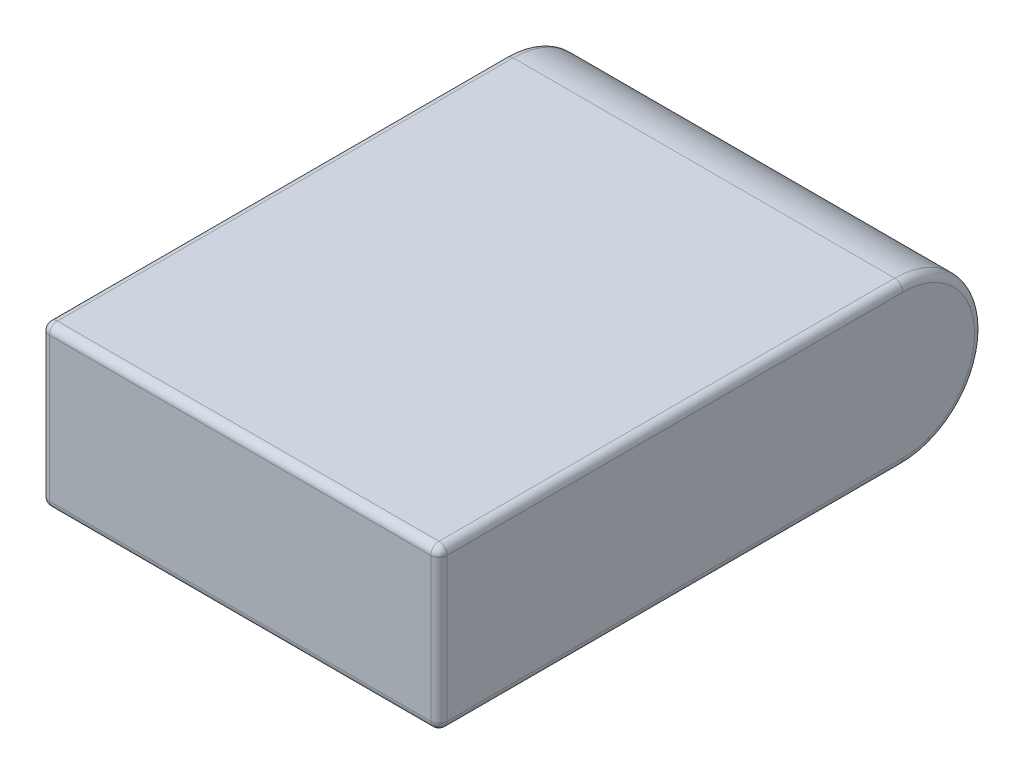
SolidWorks part; units mm, degrees
ref_plane "Front Plane" through (0, 0, 0) normal (0, 0, 1) x (1, 0, 0)
ref_plane "Top Plane" through (0, 0, 0) normal (0, 1, 0) x (1, 0, 0)
ref_plane "Right Plane" through (0, 0, 0) normal (1, 0, 0) x (0, 0, -1)
sketch "Sketch1" plane through (0, 0, 0) normal (0, 1, 0) x (1, 0, 0)
  line L1 (-24.5, 33.5) -> (24.5, 33.5)
  line L2 (-24.5, 33.5) -> (-24.5, -33.5)
  line L3 (-24.5, -33.5) -> (24.5, -33.5)
  line L4 (24.5, 33.5) -> (24.5, -33.5)
  line L5 (-24.5, 33.5) -> (24.5, -33.5) construction
  line L6 (-24.5, -33.5) -> (24.5, 33.5) construction
  point P0 (0, 0)
  dimension "D1" = 49
  dimension "D2" = 67
extrude "Boss-Extrude1" add sketch "Sketch1" against normal blind 19.7
fillet "Fillet3" radius 9.85 2 edges at (0, -19.7, -33.5) (0, 0, -33.5)
fillet "Fillet4" radius 1 12 edges at (24.5, -9.85, 33.5) (24.5, 0, 4.925) (24.5, -2.885, -30.615) (24.5, -16.815, -30.615) (24.5, -19.7, 4.925) (-24.5, 0, 4.925) (-24.5, -9.85, 33.5) (-24.5, -19.7, 4.925) (-24.5, -16.815, -30.615) (-24.5, -2.885, -30.615) (0, -19.7, 33.5) (0, 0, 33.5)
